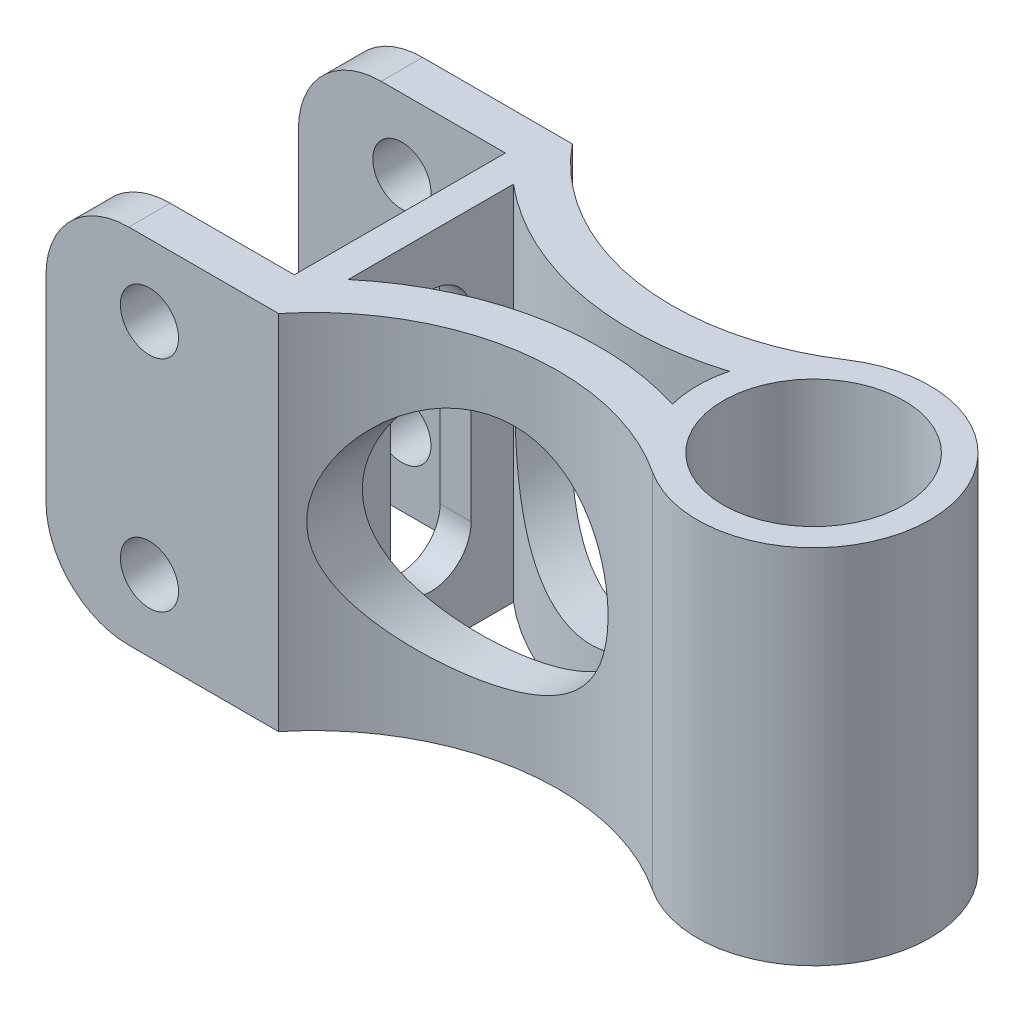
SolidWorks part; units mm, degrees
material "ABS"
ref_plane "Front" through (0, 0, 0) normal (0, 0, 1) x (1, 0, 0)
ref_plane "Top" through (0, 0, 0) normal (0, 1, 0) x (1, 0, 0)
ref_plane "Right" through (0, 0, 0) normal (1, 0, 0) x (0, 0, -1)
ref_axis "Axis1" through (0, 0, 55) along (0, 0, -1)
sketch "Sketch1" plane through (0, 0, 0) normal (0, 1, 0) x (1, 0, 0)
  line L0 (0, 0) -> (-76.2, 0) construction
  line L1 (-76.2, 18.034) -> (-76.2, -18.034) construction
  line L2 (-50.8, 12.954) -> (-50.8, -12.954)
  line L3 (-76.2, 18.034) -> (-50.8, 18.034)
  line L4 (-76.2, 18.034) -> (-76.2, 12.954)
  line L5 (-76.2, 12.954) -> (-50.8, 12.954)
  line L6 (-50.8, 18.034) -> (-50.8, 12.954) construction
  line L7 (-76.2, -18.034) -> (-50.8, -18.034)
  line L8 (-76.2, -18.034) -> (-76.2, -12.954)
  line L9 (-76.2, -12.954) -> (-50.8, -12.954)
  line L10 (-50.8, -18.034) -> (-50.8, -12.954) construction
  line L11 (-50.8, 18.034) -> (-47.6552, 18.034)
  line L12 (-46.99, 10.1417) -> (-46.99, -10.1417)
  line L13 (-47.6552, -18.034) -> (-50.8, -18.034)
  line L14 (-50.9076, 18.034) -> (-47.6552, 18.034)
  circle A0 centre (0, 0) radius 11.1
  arc A1 (-13.84, 3.503) -> (-13.84, -3.503) centre (0, 0) ccw
  arc A2 (-47.6552, 18.034) -> (-7.8584, 11.919) centre (-24.377, 36.9729) ccw
  arc A3 (-46.99, 10.1417) -> (-13.84, 3.503) centre (-24.377, 36.9729) ccw
  arc A4 (-51.5958, 14.828) -> (-5.0622, 7.6779) centre (-24.377, 36.9729) ccw construction
  arc A5 (-46.99, -10.1417) -> (-13.84, -3.503) centre (-24.377, -36.9729) cw
  arc A6 (-47.6552, -18.034) -> (-7.8584, -11.919) centre (-24.377, -36.9729) cw
  arc A7 (-7.8584, -11.919) -> (-7.8584, 11.919) centre (0, 0) ccw
  point P7 (-76.2, 0)
  dimension "D2" = 22.2
  dimension "D12" = 14.2765
  dimension "D3" = 25.4
  dimension "D4" = 5.08
  dimension "D5" = 25.908
  dimension "D6" = 50.8
  dimension "D8" = 3.81
  dimension "D10" = 3.503
  dimension "D11" = 50.9076
  dimension "D7" = 5.08
extrude "Boss-Extrude1" add sketch "Sketch1" along normal blind 44.45 contours A6 A7 A2 L11 L3 L4 L5 L2 L9 L8 L7 L13 A0 A5 L12 A3 A1 region at (-63.5, 0, -13.928)
sketch "Sketch2" plane through (-50.8, 0, 0) normal (-1, 0, 0) x (0, 0, 1)
  line L0 (0, 44.45) -> (0, 0) construction
  line L1 (-12.954, 44.45) -> (12.954, 44.45) construction
  line L2 (-12.954, 0) -> (12.954, 0) construction
  line L3 (0, 33.2988) -> (0, 11.1512) construction
  line L4 (4.9445, 33.2988) -> (4.9445, 11.1512)
  line L5 (-4.9445, 33.2988) -> (-4.9445, 11.1512)
  arc A0 (4.9445, 33.2988) -> (-4.9445, 33.2988) centre (0, 33.2988) ccw
  arc A1 (-4.9445, 11.1512) -> (4.9445, 11.1512) centre (0, 11.1512) ccw
  point P8 (0, 22.225)
  dimension "D1" = 4.9445
  dimension "D2" = 11.1512
extrude "Cut-Extrude1" cut sketch "Sketch2" against normal up to next
sketch "Sketch3" plane through (0, 0, 18.034) normal (0, 0, 1) x (1, 0, 0)
  line L0 (-76.2, 22.225) -> (14.2765, 22.225) construction
  line L1 (-76.2, 44.45) -> (-76.2, 0) construction
  line L2 (14.2765, 0) -> (14.2765, 44.45) construction
  circle A0 centre (-31.75, 22.225) radius 14.2875
  dimension "D1" = 28.575
  dimension "D2" = 44.45
extrude "Cut-Extrude2" cut sketch "Sketch3" against normal blind 50.8
hole_wizard "1/4 Clearance Hole1" positions "Sketch6" profile "Sketch7" hole size "1/4" standard "ANSI Inch" end condition through all
sketch "Sketch6" plane through (0, 0, 18.034) normal (0, 0, 1) x (1, 0, 0)
  line L0 (-63.5, 44.45) -> (-63.5, 0) construction
  line L4 (-76.2, 22.225) -> (-47.6552, 22.225) construction
  line L5 (-76.2, 44.45) -> (-76.2, 0) construction
  line L6 (-47.6552, 44.45) -> (-47.6552, 0) construction
  point P0 (-63.5, 35.687)
  point P2 (-63.5, 8.763)
  dimension "D1" = 26.924
  dimension "D2" = 12.7
sketch "Sketch7" plane through (-63.5, 35.687, 18.034) normal (1, 0, 0) x (0, -1, 0)
  line L0 (0, 0) -> (0, 36.068)
  line L1 (0, 36.068) -> (3.5712, 36.068)
  line L2 (3.5712, 36.068) -> (3.5712, 0)
  line L5 (3.5712, 0) -> (0, 0)
  line L11 (0, -6.35) -> (0, 107.95) construction
  dimension "Thru Hole Dia." = 7.1425
  dimension "Thru Hole Depth" = 36.068
fillet "Fillet5" radius 10.16 4 edges at (-76.2, 0, -15.494) (-76.2, 0, 15.494) (-76.2, 44.45, -15.494) (-76.2, 44.45, 15.494)
